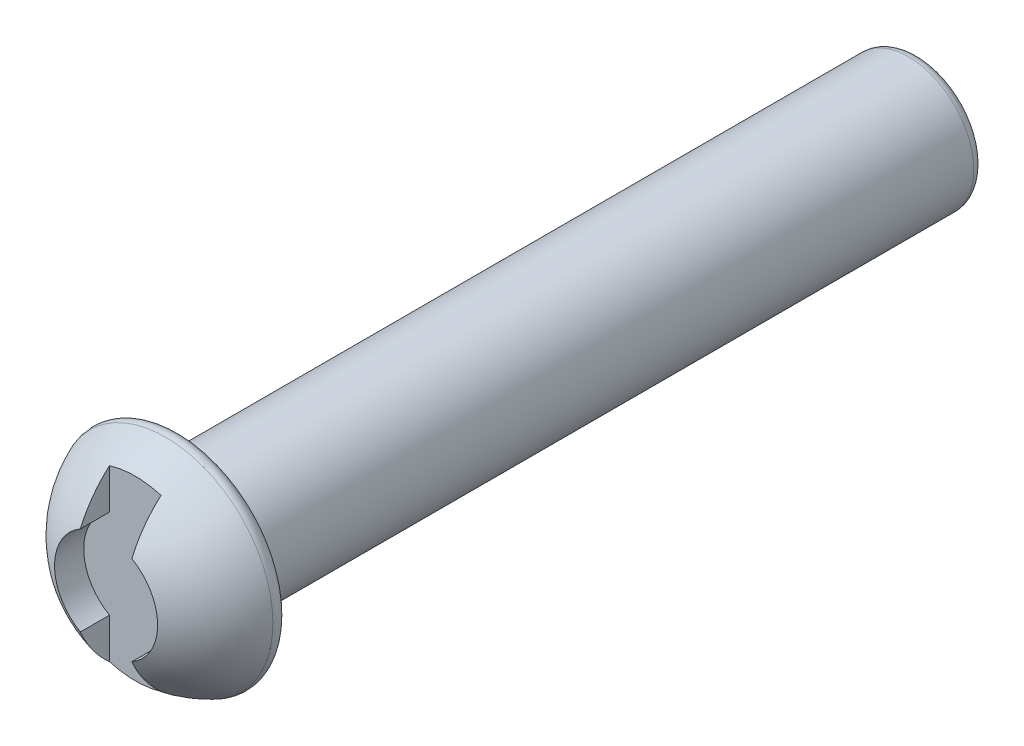
SolidWorks part; units mm, degrees
ref_plane "Front Plane" through (0, 0, 0) normal (0, 0, 1) x (1, 0, 0)
ref_plane "Top Plane" through (0, 0, 0) normal (0, 1, 0) x (1, 0, 0)
ref_plane "Right Plane" through (0, 0, 0) normal (1, 0, 0) x (0, 0, -1)
sketch "Sketch1" plane through (0, 0, 0) normal (1, 0, 0) x (0, 0, -1)
  line L0 (0, 0) -> (12, 0)
  line L1 (12, 0) -> (12, 0.95)
  line L2 (12, 0.95) -> (1.25, 0.95)
  line L3 (1.25, 0.95) -> (1.25, 1.63)
  arc A1 (1.25, 1.63) -> (0, 0) centre (1.6878, 0) ccw
  dimension "D1" = 12
  dimension "D2" = 0.95
  dimension "D3" = 1.63
  dimension "D4" = 1.25
revolve "Revolve1" add sketch "Sketch1" angle 360 about L0
sketch "Sketch2" plane through (0, 0, 0) normal (0, 0, 1) x (1, 0, 0)
  line L0 (-0.375, 0.6495) -> (-0.375, 1.9464)
  line L1 (-0.375, -1.9464) -> (0.375, -1.9464)
  line L2 (-0.375, -1.9464) -> (-0.375, -0.6495)
  line L3 (-0.375, 1.9464) -> (0.375, 1.9464)
  line L4 (0.375, -1.9464) -> (0.375, -0.6495)
  line L5 (-0.375, -1.9464) -> (0.375, 1.9464) construction
  line L6 (-0.375, 1.9464) -> (0.375, -1.9464) construction
  line L7 (0.375, 0.6495) -> (0.375, 1.9464)
  arc A0 (-0.375, 0.6495) -> (-0.375, -0.6495) centre (0, 0) ccw
  arc A1 (0.375, -0.6495) -> (0.375, 0.6495) centre (0, 0) ccw
  point P0 (0, 0)
  dimension "D2" = 1.5
  dimension "D1" = 0.75
extrude "Cut-Extrude1" cut sketch "Sketch2" against normal blind 0.6
fillet "Fillet1" radius 0.15 1 edges at (0.95, 0, -12)
fillet "Fillet2" radius 0.15 1 edges at (1.63, 0, -1.25)
